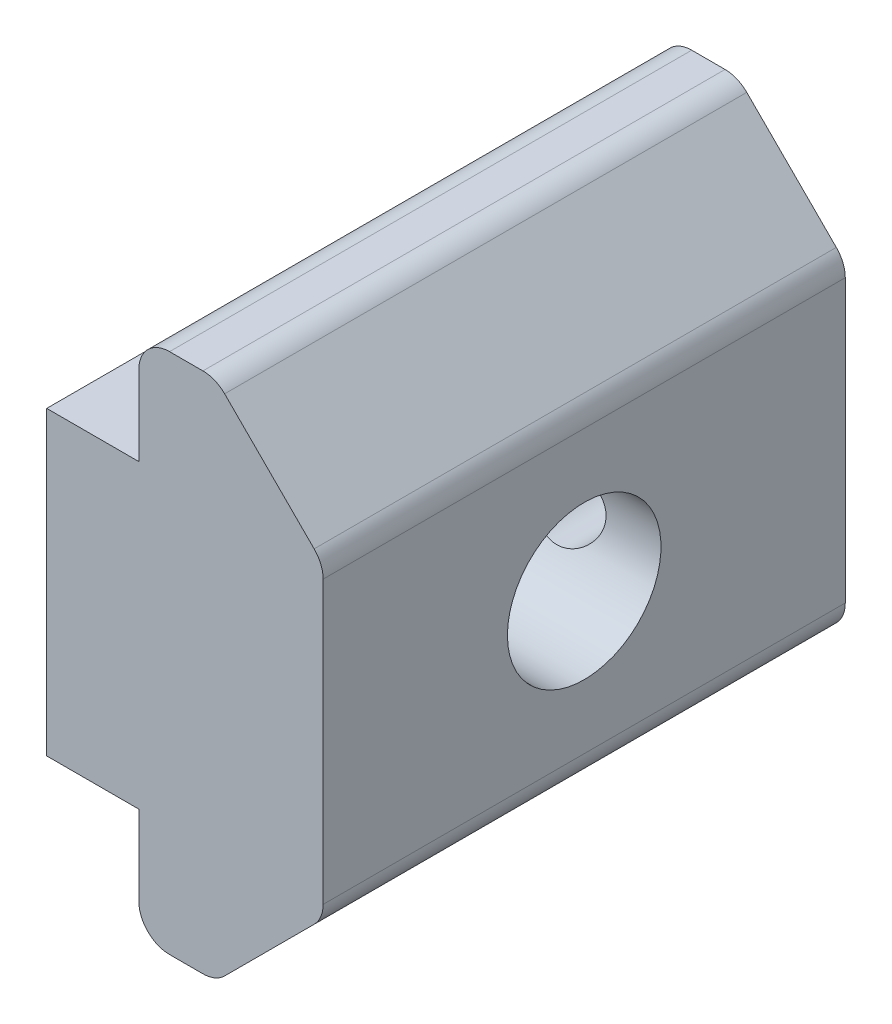
SolidWorks part; units mm, degrees
ref_plane "Front Plane" through (0, 0, 0) normal (0, 0, 1) x (1, 0, 0)
ref_plane "Top Plane" through (0, 0, 0) normal (0, 1, 0) x (1, 0, 0)
ref_plane "Right Plane" through (0, 0, 0) normal (1, 0, 0) x (0, 0, -1)
sketch "Model" plane through (0, 0, 0) normal (0, 0, 1) x (1, 0, 0)
  line L0 (64.2929, 21.7929) -> (67.2071, 24.7071)
  line L1 (63.5858, 21.5) -> (62.5, 21.5)
  line L2 (67.5, 25.4142) -> (67.5, 34.5858)
  line L3 (61.5, 25.1) -> (58.5, 25.1)
  line L4 (61.5, 34.9) -> (58.5, 34.9)
  line L9 (58.5, 25.1) -> (58.5, 34.9)
  line L11 (61.5, 22.5) -> (61.5, 25.1)
  line L12 (64.2929, 38.2071) -> (67.2071, 35.2929)
  line L13 (61.5, 34.9) -> (61.5, 37.5)
  line L14 (63.5858, 38.5) -> (62.5, 38.5)
  arc A0 (61.5, 22.5) -> (62.5, 21.5) centre (62.5, 22.5) ccw
  arc A1 (63.5858, 21.5) -> (64.2929, 21.7929) centre (63.5858, 22.5) ccw
  arc A2 (64.2929, 38.2071) -> (63.5858, 38.5) centre (63.5858, 37.5) ccw
  arc A3 (62.5, 38.5) -> (61.5, 37.5) centre (62.5, 37.5) ccw
  arc A4 (67.2071, 24.7071) -> (67.5, 25.4142) centre (66.5, 25.4142) ccw
  arc A5 (67.5, 34.5858) -> (67.2071, 35.2929) centre (66.5, 34.5858) ccw
extrude "Boss-Extrude2" add sketch "Model" along normal blind 8.5 and the other way blind 8.5
sketch "Sketch2" plane through (58.5, 0, 0) normal (-1, 0, 0) x (0, 0, 1)
  line L0 (-8.5, 38.5) -> (8.5, 38.5) construction
  line L1 (8.5, 34.9) -> (8.5, 25.1) construction
  point P0 (0, 30)
  dimension "D1" = 8.5
  dimension "D2" = 8.5
hole_wizard "M6 Tapped Hole1" positions "Sketch4" profile "Sketch3" tap size "M6" standard "ISO" end condition through all
sketch "Sketch4" plane through (58.5, 0, 0) normal (-1, 0, 0) x (0, 0, 1)
  point P0 (0, 30)
sketch "Sketch3" plane through (58.5, 30, 0) normal (0, 1, 0) x (0, 0, 1)
  line L0 (0, 0) -> (0, 9)
  line L1 (0, 9) -> (2.5, 9)
  line L2 (2.5, 9) -> (2.5, 0)
  line L5 (2.5, 0) -> (0, 0)
  line L11 (0, -6.35) -> (0, 107.95) construction
  dimension "Thru Tap Drill Dia." = 5
  dimension "Thru Tap Drill Depth" = 9
cosmetic thread "Hole Thread1" parameters "D2"=6
sketch "Sketch5" plane through (0, 0, -8.5) normal (0, 0, -1) x (-1, 0, 0)
  line L0 (-61.5, 34.9) -> (-67.4239, 25.0315)
  line L1 (-67.4239, 25.0315) -> (-67.4239, 34.9685)
  line L2 (-67.4239, 34.9685) -> (-61.5, 25.1)
  arc A0 (-67.5, 25.4142) -> (-67.2071, 24.7071) centre (-66.5, 25.4142) ccw construction
  arc A1 (-67.2071, 35.2929) -> (-67.5, 34.5858) centre (-66.5, 34.5858) ccw construction
  point P6 (-64.4619, 29.9658)
hole_wizard "M3x0.5 Tapped Hole1" positions "Sketch7" profile "Sketch6" tap size "M3x0.5" standard "ANSI Metric"
sketch "Sketch7" plane through (0, 0, -8.5) normal (0, 0, -1) x (-1, 0, 0)
  point P0 (-64.4619, 29.9658)
sketch "Sketch6" plane through (64.4619, 29.9658, -8.5) normal (1, 0, 0) x (0, 1, 0)
  line L0 (0, 0) -> (0, 8.2511)
  line L1 (0, 8.2511) -> (1.25, 7.5)
  line L2 (1.25, 7.5) -> (1.25, 0)
  line L5 (1.25, 0) -> (0, 0)
  line L10 (0, 8.2511) -> (-1.25, 7.5) construction
  line L11 (0, -6.35) -> (0, 107.95) construction
  dimension "Tap Drill Dia." = 2.5
  dimension "Tap Drill Depth" = 7.5
  dimension "Drill Angle" = 118
cosmetic thread "Hole Thread2" parameters "D1"=6, "D2"=3
